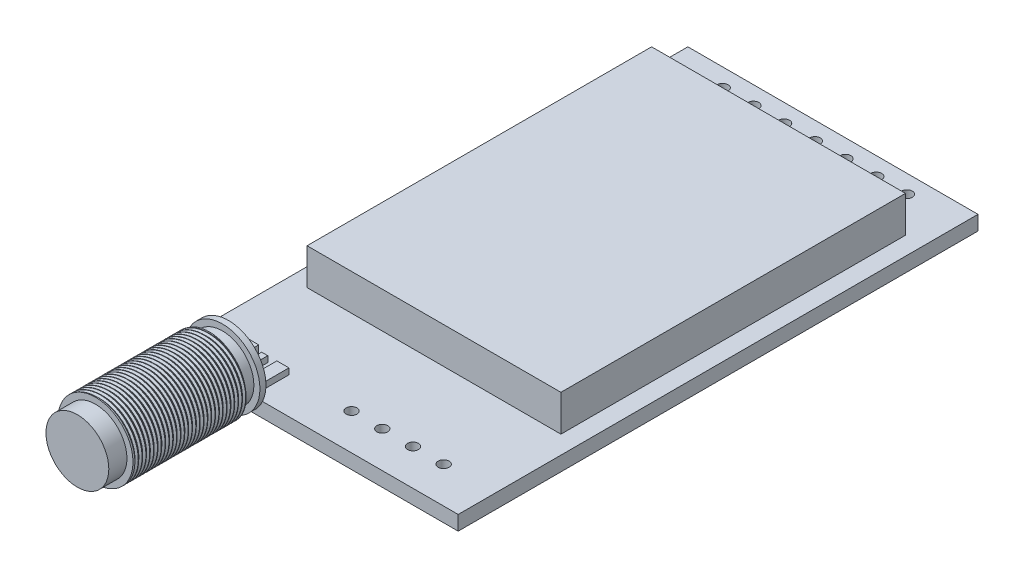
SolidWorks part; units mm, degrees
ref_plane "Ön Düzlem" through (0, 0, 0) normal (0, 0, 1) x (1, 0, 0)
ref_plane "Üst Düzlem" through (0, 0, 0) normal (0, 1, 0) x (1, 0, 0)
ref_plane "Sağ Düzlem" through (0, 0, 0) normal (1, 0, 0) x (0, 0, -1)
sketch "Çizim1" plane through (0, 0, 0) normal (0, 1, 0) x (1, 0, 0)
  line L1 (-12, 21.5) -> (12, 21.5)
  line L2 (-12, 21.5) -> (-12, -21.5)
  line L3 (-12, -21.5) -> (12, -21.5)
  line L4 (12, 21.5) -> (12, -21.5)
  line L5 (-12, 21.5) -> (12, -21.5) construction
  line L6 (-12, -21.5) -> (12, 21.5) construction
  point P0 (0, 0)
  dimension "D1" = 24
  dimension "D2" = 43
extrude "Yükseklik-Ekstrüzyon1" add sketch "Çizim1" along normal blind 1.2
sketch "Çizim2" plane through (0, 1.2, 0) normal (0, 1, 0) x (1, 0, 0)
  line L0 (12, 21.5) -> (-12, 21.5) construction
  line L1 (-10.5, 17) -> (10.5, 17)
  line L2 (-10.5, 17) -> (-10.5, -11.5)
  line L4 (10.5, 17) -> (10.5, -11.5)
  line L5 (-12, -21.5) -> (12, -21.5) construction
  line L6 (12, -21.5) -> (12, 21.5) construction
  line L7 (-12, 21.5) -> (-12, -21.5) construction
  line L8 (-10.5, -11.5) -> (10.5, -11.5)
  point P0 (0, 0)
  dimension "D1" = 4.5
  dimension "D2" = 1.5
  dimension "D3" = 10
  dimension "D4" = 1.5
extrude "Yükseklik-Ekstrüzyon2" add sketch "Çizim2" along normal blind 3
sketch "Çizim3" plane through (0, 1.2, 0) normal (0, 1, 0) x (1, 0, 0)
  line L0 (-12, 21.5) -> (-12, -21.5) construction
  line L1 (12, 21.5) -> (-12, 21.5) construction
  line L3 (-12, -21.5) -> (12, -21.5) construction
  line L4 (12, -21.5) -> (12, 21.5) construction
  circle A0 centre (-7.62, 20) radius 0.45
  circle A1 centre (-5.08, 20) radius 0.45
  circle A2 centre (-2.54, 20) radius 0.45
  circle A3 centre (0, 20) radius 0.45
  circle A4 centre (2.54, 20) radius 0.45
  circle A5 centre (5.08, 20) radius 0.45
  circle A6 centre (7.62, 20) radius 0.45
  circle A13 centre (7.8, -18.5) radius 0.45
  circle A14 centre (5.26, -18.5) radius 0.45
  circle A15 centre (2.72, -18.5) radius 0.45
  circle A16 centre (0.18, -18.5) radius 0.45
  dimension "D2" = 1.5
  dimension "D3" = 0.9
  dimension "D6" = 3
  dimension "D7" = 4.2
  dimension "D5" = 0.9
  dimension "D1" = 4.38
  dimension "D4" = 7
  dimension "D8" = 4
extrude "Kes-Ekstrüzyon1" cut sketch "Çizim3" against normal blind 3
sketch "Çizim4" plane through (0, 0, 21.5) normal (0, 0, 1) x (1, 0, 0)
  line L0 (-12, 0) -> (12, 0) construction
  circle A0 centre (-7, 2.5) radius 3.1
  dimension "D1" = 6.2
  dimension "D2" = 2.5
  dimension "D3" = 5
extrude "Yükseklik-Ekstrüzyon3" add sketch "Çizim4" along normal blind 0.5
sketch "Çizim5" plane through (0, 0, 22) normal (0, 0, 1) x (1, 0, 0)
  circle A3 centre (-7, 2.5) radius 2.6
  circle A4 centre (-7, 2.5) radius 2.6
  dimension "D1" = 0.5
extrude "Yükseklik-Ekstrüzyon4" add sketch "Çizim5" along normal blind 1
sketch "Çizim6" plane through (0, 0, 23) normal (0, 0, 1) x (1, 0, 0)
  circle A2 centre (-7, 2.5) radius 3.1
  circle A3 centre (-7, 2.5) radius 3.1
  dimension "D1" = 0.5
extrude "Yükseklik-Ekstrüzyon5" add sketch "Çizim6" along normal blind 11
sketch "Çizim7" plane through (0, 0, 34) normal (0, 0, 1) x (1, 0, 0)
  circle A2 centre (-7, 2.5) radius 2.6
  circle A3 centre (-7, 2.5) radius 2.6
  circle A4 centre (-7, 2.5) radius 3.1
  circle A5 centre (-7, 2.5) radius 3.1
  dimension "D1" = 0.5
  dimension "D2" = 0
extrude "Kes-Ekstrüzyon2" cut sketch "Çizim7" against normal blind 1.5
sketch "Çizim8" plane through (0, 0, 32.5) normal (0, 0, 1) x (1, 0, 0)
  circle A1 centre (-7, 2.5) radius 3.1
  circle A2 centre (-7, 2.5) radius 3.1
  dimension "D1" = 0
curve "Helis/Spiral1" pitch 0.2 height 10 turns 50
ref_plane "Düzlem1" through (-7, 0, 0) normal (1, 0, 0) x (0, 0, -1)
sketch "Çizim9" plane through (-7, 0, 0) normal (1, 0, 0) x (0, 0, -1)
  line L0 (-32.5, 5.6138) -> (-32.45, 5.6138)
  line L2 (-32.45, 5.6138) -> (-32.5, 5.4138)
  line L3 (-32.5, 5.4138) -> (-32.55, 5.6138)
  line L4 (-32.55, 5.6138) -> (-32.5, 5.6138)
  line L5 (-32.5, 5.6) -> (-32.5, 5.6311) construction
  line L6 (-32.5, 5.6) -> (-32.5, -0.6) construction
  dimension "D1" = 0.05
  dimension "D2" = 0.05
  dimension "D3" = 0.2
thread "Diş1" pitch 0.3175 method cut profile "Diş Profili1" start angle 0, offset 0, length 10, pitch 0.3175, diameter 6.2
ref_plane "Düzlem2" through (-10.1, 2.5, 32.5) normal (0, -1, 0) x (-1, 0, 0)
sketch "Diş Profili1" plane through (-10.1, 2.5, 32.5) normal (0, -1, 0) x (-1, 0, 0)
  line L0 (0, 0) -> (0, 0.3175) construction
  line L11 (0, 0) -> (0, 0.2778)
  line L12 (0, 0.2778) -> (-0.1719, 0.1786)
  line L13 (-0.1719, 0.1786) -> (-0.1719, 0.0992)
  line L15 (-0.1719, 0.0992) -> (0, 0)
  line L17 (-0.1719, 0.1389) -> (0, 0.1389) construction
  point P2 (0, 0)
  dimension "Pitch" = 0.3175
  dimension "Profile_Angle" = 60
  dimension "Profile_Land" = 0.0794
  dimension "Profile_Height" = 0.1719
sketch "Çizim12" plane through (-12, 0, 0) normal (-1, 0, 0) x (0, 0, 1)
  line L0 (21.5, 4.6) -> (21.5, 1.2)
  line L1 (21.5, 5.6) -> (21.5, 1.2) construction
  line L2 (21.5, 1.2) -> (18.5, 1.2)
  line L3 (-21.5, 1.2) -> (21.5, 1.2) construction
  line L4 (18.5, 1.2) -> (18.5, 1.7)
  line L5 (18.5, 1.7) -> (21, 1.7)
  line L6 (21, 1.7) -> (21, 4.6)
  line L7 (21, 4.6) -> (21.5, 4.6)
  line L8 (22, 5.6) -> (21.5, 5.6) construction
  dimension "D1" = 0.5
  dimension "D2" = 0.5
  dimension "D3" = 1
  dimension "D4" = 3
extrude "Yükseklik-Ekstrüzyon6" add sketch "Çizim12" against normal blind 1 from offset 6 offset against normal yes
pattern_linear "LÇoğaltma1" count 2 spacing 3 along (-1, 0, 0) of "Yükseklik-Ekstrüzyon6"
sketch "Çizim13" plane through (-12, 0, 0) normal (-1, 0, 0) x (0, 0, 1)
  line L0 (21.5, 4.6) -> (21, 4.6)
  line L1 (21, 4.6) -> (21, 1.7)
  line L2 (21, 1.7) -> (18.5, 1.7)
  line L3 (18.5, 1.7) -> (18.5, 1.2)
  line L4 (18.5, 1.2) -> (21.5, 1.2)
  line L5 (21.5, 1.2) -> (21.5, 4.6)
extrude "Yükseklik-Ekstrüzyon7" add sketch "Çizim13" against normal blind 0.5 from offset 4.75 offset against normal yes
